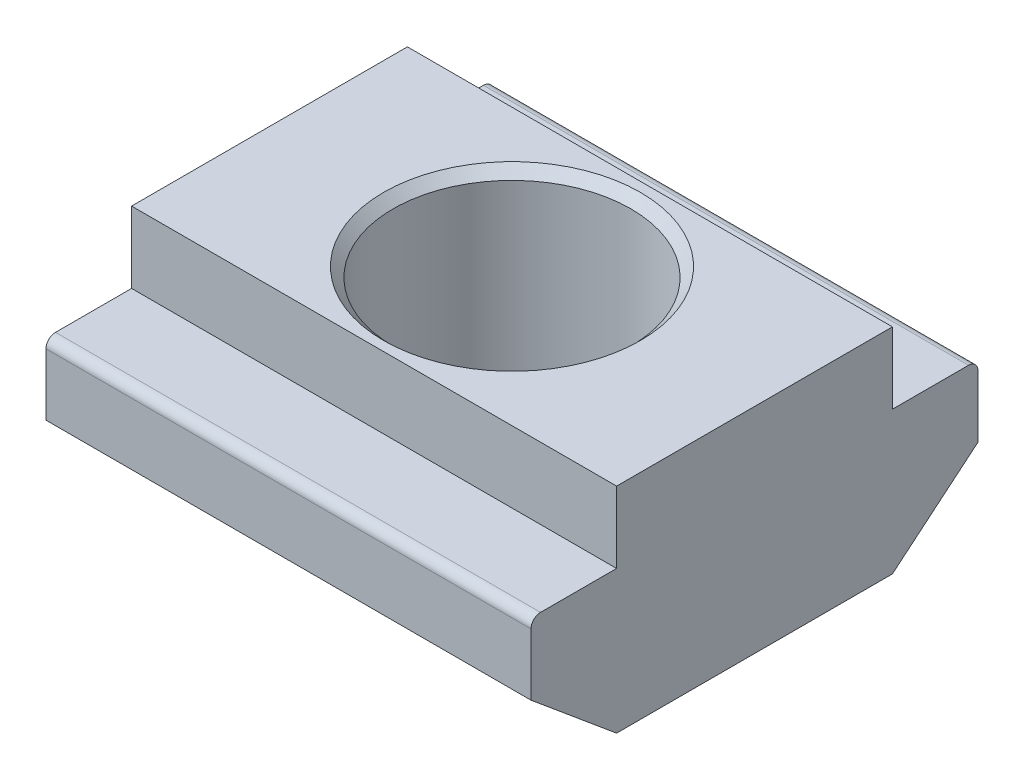
SolidWorks part; units mm, degrees
material "AISI 316 Stainless Steel Sheet (SS)"
ref_plane "Спереди" through (0, 0, 0) normal (0, 0, 1) x (1, 0, 0)
ref_plane "Сверху" through (0, 0, 0) normal (0, 1, 0) x (1, 0, 0)
ref_plane "Справа" through (0, 0, 0) normal (1, 0, 0) x (0, 0, -1)
sketch "Эскиз1" plane through (0, 0, 0) normal (1, 0, 0) x (0, 0, -1)
  line L0 (-2.9, 0) -> (2.9, 0)
  line L1 (-2.9, 0) -> (-4.7, 1.5)
  line L2 (-4.7, 1.5) -> (-4.7, 3)
  line L3 (-4.7, 3) -> (-2.9, 3)
  line L4 (-2.9, 3) -> (-2.9, 4.5)
  line L5 (-2.9, 4.5) -> (2.9, 4.5)
  line L6 (2.9, 4.5) -> (2.9, 3)
  line L7 (2.9, 3) -> (4.7, 3)
  line L8 (4.7, 3) -> (4.7, 1.5)
  line L9 (4.7, 1.5) -> (2.9, 0)
  line L10 (0, 0) -> (0, 3.8912) construction
  point P4 (0, 0)
  dimension "D1" = 5.8
  dimension "D2" = 4.5
  dimension "D3" = 1.5
  dimension "D4" = 1.5
  dimension "D5" = 1.5
  dimension "D6" = 1.5
  dimension "D7" = 5.8
  dimension "D8" = 9.4
extrude "Body" add sketch "Эскиз1" along normal blind 10.2
sketch "Эскиз2" plane through (0, 4.5, 0) normal (0, 1, 0) x (1, 0, 0)
  line L0 (0, 0) -> (10.8879, 0) construction
  line L1 (5.1, 4.7) -> (5.1, -4.7) construction
  line L2 (10.2, 4.7) -> (0, 4.7) construction
  line L3 (10.2, -4.7) -> (0, -4.7) construction
  circle A0 centre (5.1, 0) radius 2.5
  dimension "D1" = 5
extrude "screwHole" cut sketch "Эскиз2" against normal blind 10.2
chamfer "Chamfer" distance 0.2 angle 45 1 edges at (5.1, 4.5, 2.5)
fillet "Fillet" radius 0.2 2 edges at (5.1, 3, 4.7) (5.1, 3, -4.7)
